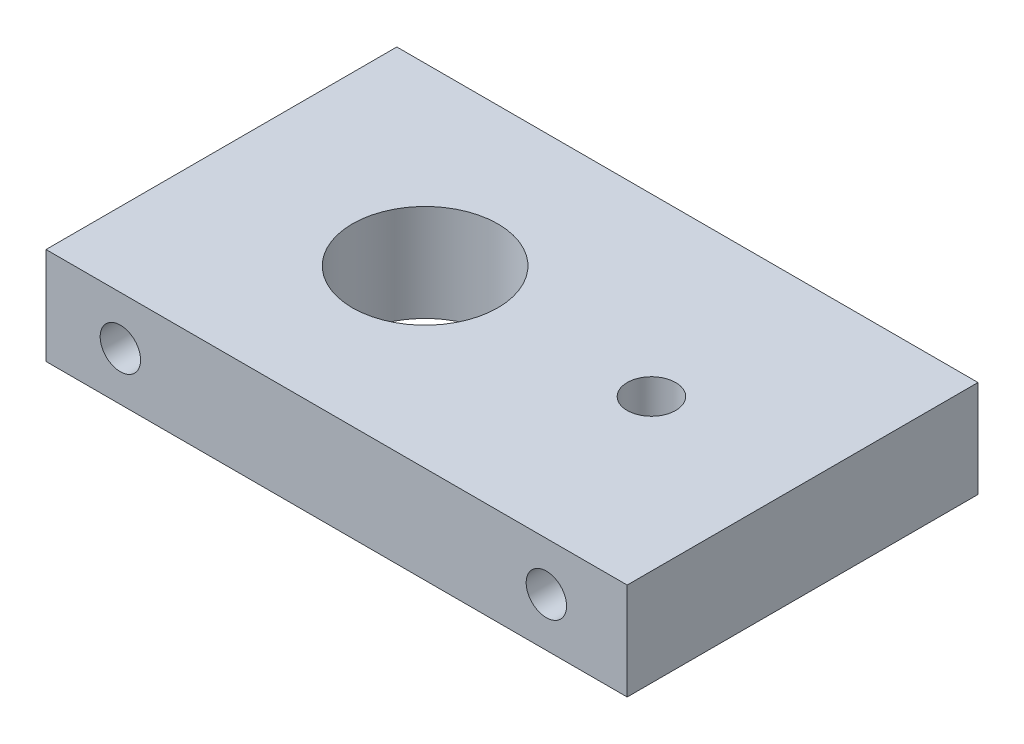
SolidWorks part; units mm, degrees
ref_plane "Ebene vorne" through (0, 0, 0) normal (0, 0, 1) x (1, 0, 0)
ref_plane "Ebene oben" through (0, 0, 0) normal (0, 1, 0) x (1, 0, 0)
ref_plane "Ebene rechts" through (0, 0, 0) normal (1, 0, 0) x (0, 0, -1)
sketch "Skizze1" plane through (0, 0, 0) normal (0, 0, 1) x (1, 0, 0)
  line L1 (-23.35, 231) -> (23.35, 231)
  line L2 (-23.35, 231) -> (-23.35, 237)
  line L3 (-23.35, 237) -> (23.35, 237)
  line L4 (23.35, 231) -> (23.35, 237)
  line L5 (-23.35, 231) -> (23.35, 237) construction
  line L6 (-23.35, 237) -> (23.35, 231) construction
  point P0 (0, 234)
sketch "Skizze2" plane through (0, 0, 0) normal (0, 1, 0) x (1, 0, 0)
  line L1 (-12.6, 12.65) -> (25.15, 12.65)
  line L2 (25.15, 12.65) -> (25.15, -12.65)
  line L3 (25.15, -12.65) -> (-12.6, -12.65)
  line L5 (-12.6, 10.85) -> (23.35, 10.85)
  line L6 (23.35, 10.85) -> (23.35, -10.85)
  line L7 (23.35, -10.85) -> (-12.6, -10.85)
  arc A0 (-12.6, 12.65) -> (-12.6, -12.65) centre (-12.6, 0) ccw
  arc A1 (-12.6, 10.85) -> (-12.6, -10.85) centre (-12.6, 0) ccw
sketch "Skizze3" plane through (0, 0, 0) normal (0, 0, 1) x (1, 0, 0)
  line L1 (-23.35, 231) -> (23.35, 231)
  line L2 (-23.35, 231) -> (-23.35, 237)
  line L3 (-23.35, 237) -> (23.35, 237)
  line L4 (23.35, 231) -> (23.35, 237)
  line L5 (-23.35, 231) -> (23.35, 237) construction
  line L6 (-23.35, 237) -> (23.35, 231) construction
  point P0 (0, 234)
extrude "Aufsatz-Linear austragen1" add sketch "Skizze3" along normal up to vertex (12.65 mm away) and the other way up to vertex (12.65 mm away) up to point (25.15, 0, 12.65) other way up to point (25.15, 0, -12.65)
sketch "Skizze4" plane through (0, 0, 0) normal (0, 1, 0) x (1, 0, 0)
  line L0 (23.35, -10.85) -> (23.35, 10.85)
  line L1 (23.35, 10.85) -> (23.35, -10.85) construction
  line L2 (23.35, 10.85) -> (-12.6, 10.85)
  line L3 (-76.8863, 0) -> (76.8863, 0) construction
  line L4 (23.35, -10.85) -> (-12.6, -10.85)
  line L5 (-12.6, 10.85) -> (-12.6, -10.85)
  point P15 (23.35, 0)
extrude "Schnitt-Linear austragen1" cut sketch "Skizze4" along normal up to surface (237 mm away) flip side to cut up to face at (0, 237, 0)
sketch "HoleLeadscrewLinearGuide" plane through (0, 0, 0) normal (0, 1, 0) x (1, 0, 0)
  circle A0 centre (14, 0) radius 1.5
  circle A1 centre (0, 0) radius 4.5
sketch "Skizze7" plane through (0, 0, 0) normal (0, 1, 0) x (1, 0, 0)
  circle A0 centre (0, 0) radius 4.5
  circle A1 centre (14, 0) radius 1.5
extrude "Schnitt-Linear austragen2" cut sketch "Skizze7" along normal up to surface (237 mm away) up to face at (5.375, 237, 0)
sketch "ThreadHolesSide" plane through (0, 0, 0) normal (0, 0, 1) x (1, 0, 0)
  line L0 (0, 234) -> (28.7572, 234) construction
  line L3 (0, 615) -> (28.7572, 615) construction
  circle A0 centre (18.35, 234) radius 1.25
  circle A1 centre (-8, 234) radius 1.25
  circle A2 centre (19.35, 615) radius 1.25
  circle A3 centre (-8, 615) radius 1.25
extrude "Schnitt-Linear austragen3" cut sketch "ThreadHolesSide" along normal blind 6 from surface starting at face at (5.375, 234, -10.85)
extrude "Schnitt-Linear austragen4" cut sketch "ThreadHolesSide<2>" against normal blind 6 from surface starting at face at (5.375, 234, 10.85)
sketch "ThreadHolesSide<2>" plane through (0, 0, 0) normal (0, 0, 1) x (1, 0, 0) same geometry as "ThreadHolesSide"
